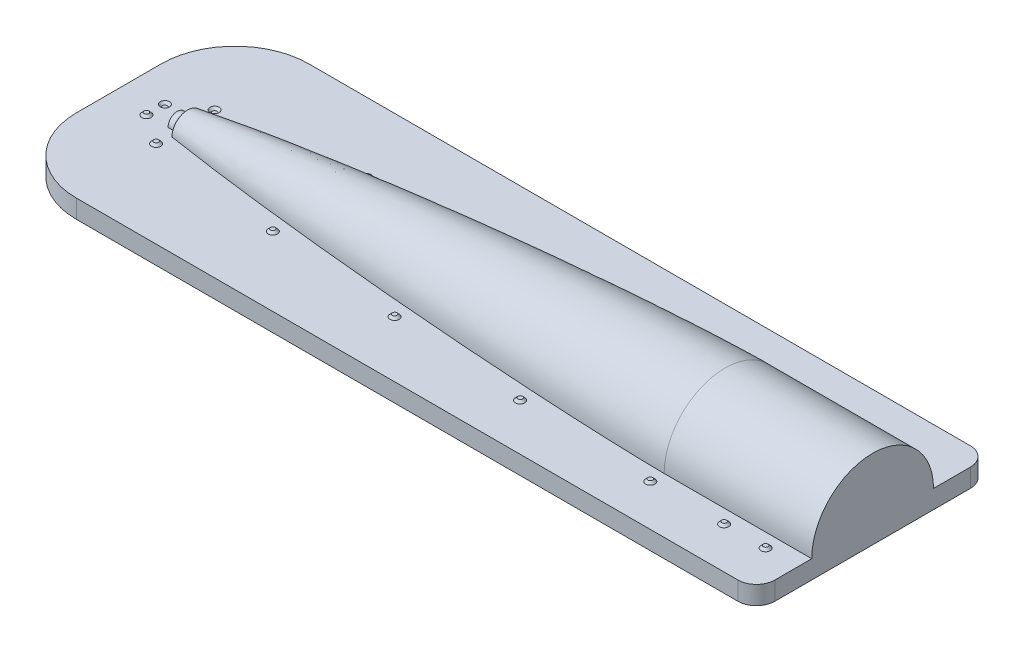
SolidWorks part; units mm, degrees
ref_plane "Front" through (0, 0, 0) normal (0, 0, 1) x (1, 0, 0)
ref_plane "Top" through (0, 0, 0) normal (0, 1, 0) x (1, 0, 0)
ref_plane "Right" through (0, 0, 0) normal (1, 0, 0) x (0, 0, -1)
other "von Karman body"
sketch "Sketch1" plane through (0, 0, 0) normal (0, 1, 0) x (1, 0, 0)
  line L0 (838.2, 83.82) -> (1041.4, 83.82)
  line L1 (1041.4, 83.82) -> (1055.402, 4.4107)
  line L2 (1055.7879, 0) -> (79.7661, 0)
  line L3 (96.6803, 12.7) -> (83.9803, 12.7)
  line L4 (96.6803, 12.7) -> (98.2259, 21.4654)
  line L5 (83.9803, 12.7) -> (80.7329, 4.8601)
  line L6 (0, 0) -> (1055.7879, 0) construction
  line L7 (83.9803, 12.7) -> (82.9291, 18.9624) construction
  line L8 (79.7661, 0) -> (79.7661, 6.839) construction
  circle A0 centre (3.2859, 0) radius 1.5875 construction
  arc A1 (80.7329, 4.8601) -> (79.7661, 0) centre (92.4661, 0) ccw
  arc A2 (1055.402, 4.4107) -> (1055.7879, 0) centre (1030.3879, 0) cw
  spline S0 degree 4 poles (0.0014, -0.0139) (0.0044, -0.0057) (0.0116, 0.0101) (0.0314, 0.0387) (0.0663, 0.0774) (0.1098, 0.1198) (0.1756, 0.1763) (0.2578, 0.2402) (0.43, 0.3617) (0.6491, 0.4956) (0.898, 0.6345) (1.1966, 0.7887) (1.4641, 0.9197) (1.9053, 1.1256) (2.6908, 1.4661) (4.1174, 2.0276) (6.8315, 2.9752) (11.8195, 4.4991) (21.1817, 6.9737) (37.5192, 10.6769) (65.2764, 16.0894) (103.3878, 22.4749) (149.5828, 29.2977) (200.9556, 36.0951) (252.4018, 42.3062) (303.9044, 48.03) (355.4522, 53.3298) (407.0382, 58.2429) (458.6575, 62.7928) (510.3066, 66.9901) (561.9831, 70.8361) (613.6852, 74.3214) (665.4118, 77.4242) (710.6933, 79.7692) (749.5207, 81.4699) (780.8317, 82.597) (801.9098, 83.2137) (819.2261, 83.6007) (830.0679, 83.7618) (835.4892, 83.8132) (838.2, 83.82) knots 0 0 0 0 0 0.000041 0.000082 0.000164 0.000247 0.000329 0.000493 0.000658 0.001245 0.001545 0.001844 0.002251 0.002657 0.003853 0.005902 0.009516 0.016281 0.028569 0.051794 0.088907 0.150314 0.211721 0.273128 0.334535 0.395942 0.457348 0.518755 0.580162 0.641569 0.702976 0.764383 0.825789 0.887196 0.9179 0.948603 0.974302 0.987151 1 1 1 1 1 construction
  spline S1 degree 4 poles (98.2259, 21.4654) (104.6543, 22.4927) (123.8878, 25.4864) (155.972, 30.1431) (200.9556, 36.0951) (252.4018, 42.3062) (303.9044, 48.03) (355.4522, 53.3298) (407.0382, 58.2429) (458.6575, 62.7928) (510.3066, 66.9901) (561.9831, 70.8361) (613.6852, 74.3214) (665.4118, 77.4242) (710.6933, 79.7692) (749.5207, 81.4699) (780.8317, 82.597) (801.9098, 83.2137) (819.2261, 83.6007) (830.0679, 83.7618) (835.4892, 83.8132) (838.2, 83.82) knots 0.119456 0.119456 0.119456 0.119456 0.119456 0.150314 0.211721 0.273128 0.334535 0.395942 0.457348 0.518755 0.580162 0.641569 0.702976 0.764383 0.825789 0.887196 0.9179 0.948603 0.974302 0.987151 1 1 1 1 1
  spline S2 degree 4 poles (0, 0) (0.003, 0.0082) (0.0102, 0.024) (0.03, 0.0526) (0.0649, 0.0913) (0.1084, 0.1337) (0.1742, 0.1902) (0.2565, 0.254) (0.4287, 0.3755) (0.6477, 0.5094) (0.8967, 0.6483) (1.1954, 0.8025) (1.4629, 0.9334) (1.9041, 1.1393) (2.6896, 1.4796) (4.1163, 2.0409) (6.8305, 2.9882) (11.8188, 4.5114) (21.1813, 6.9846) (37.5193, 10.6856) (65.2772, 16.0943) (103.3896, 22.4744) (149.5855, 29.2908) (200.9592, 36.0811) (252.4063, 42.285) (303.9097, 48.0016) (355.4582, 53.2943) (407.0449, 58.2003) (458.6648, 62.7429) (510.3146, 66.9331) (561.9916, 70.772) (613.6942, 74.2501) (665.4211, 77.3457) (710.703, 79.6843) (749.5307, 81.3797) (780.8418, 82.5024) (801.92, 83.1162) (819.2363, 83.5008) (830.0782, 83.6603) (835.4995, 83.711) (838.2103, 83.7174) knots 0 0 0 0 0 0.000041 0.000082 0.000164 0.000247 0.000329 0.000493 0.000658 0.001245 0.001545 0.001844 0.002251 0.002657 0.003853 0.005902 0.009516 0.016281 0.028569 0.051794 0.088907 0.150314 0.211721 0.273128 0.334535 0.395942 0.457348 0.518755 0.580162 0.641569 0.702976 0.764383 0.825789 0.887196 0.9179 0.948603 0.974302 0.987151 1 1 1 1 1 construction
  spline S3 degree 4 poles (0, 0) (0.003, 0.0082) (0.0102, 0.024) (0.03, 0.0526) (0.0649, 0.0913) (0.1084, 0.1337) (0.1742, 0.1902) (0.2565, 0.254) (0.4287, 0.3755) (0.6477, 0.5094) (0.8967, 0.6483) (1.1954, 0.8025) (1.4629, 0.9334) (1.9041, 1.1393) (2.6896, 1.4796) (4.1163, 2.0409) (6.8305, 2.9882) (11.8188, 4.5114) (21.1813, 6.9846) (37.5193, 10.6856) (58.8862, 14.849) (77.7757, 18.1421) (91.8621, 20.4493) (98.2259, 21.4654) knots 0 0 0 0 0 0.000041 0.000082 0.000164 0.000247 0.000329 0.000493 0.000658 0.001245 0.001545 0.001844 0.002251 0.002657 0.003853 0.005902 0.009516 0.016281 0.028569 0.051794 0.088907 0.119454 0.119454 0.119454 0.119454 0.119454 construction
  point P5 (0, 0)
  dimension "D6" = 3.175
  dimension "D9" = 25.4
  dimension "D10" = 12.7
  dimension "D1" = 12.7
  dimension "D2" = 100
  dimension "D3" = 203.2
  dimension "D4" = 6.35
  dimension "D5" = 838.2
  dimension "D7" = 67.5
  dimension "D8" = 80
  dimension "D11" = 83.82
  dimension "D12" = 12.7
revolve "main body" add sketch "Sketch1" angle 180 about L2 other way angle 180 reverse direction yes
scale "Scale1" [suppressed]
sketch "Sketch2" plane through (0, 0, 0) normal (0, -1, 0) x (1, 0, 0)
  line L0 (1055.7879, 0) -> (1131.9879, 0) construction
  line L1 (1131.9879, -160.02) -> (3.5661, -160.02)
  line L2 (1131.9879, -160.02) -> (1131.9879, 160.02)
  line L3 (1131.9879, 160.02) -> (3.5661, 160.02)
  line L4 (3.5661, -160.02) -> (3.5661, 160.02)
  line L5 (1041.4, -83.82) -> (838.2, -83.82) construction
  arc A0 (1055.402, -4.4107) -> (1055.402, 4.4107) centre (1030.3879, 0) ccw construction
  arc A1 (80.7329, 4.8601) -> (80.7329, -4.8601) centre (92.4661, 0) ccw construction
  point P17 (79.7661, 0)
  dimension "D2" = 76.2
  dimension "D1" = 76.2
  dimension "D3" = 76.2
extrude "Boss-Extrude1" add sketch "Sketch2" along normal blind 25.4
fillet "Fillet1" radius 6.35 1 edges at (96.6803, 12.7, 0)
sketch "Sketch3" plane through (0, 0, 0) normal (0, 1, 0) x (1, 0, 0)
  line L0 (79.7661, 0) -> (3.5661, 0) construction
  line L3 (3.5661, -160.02) -> (3.5661, 160.02) construction
  line L4 (95.2196, -40.2767) -> (98.2259, -21.4654) construction
  line L5 (282.229, -45.582) -> (280.1341, -64.5165) construction
  line L6 (465.7678, -82.4343) -> (467.3539, -63.4504) construction
  line L7 (651.796, -95.6427) -> (652.8954, -76.6245) construction
  line L8 (838.1523, -102.8699) -> (838.2, -83.82) construction
  line L9 (1041.4, -83.82) -> (838.2, -83.82) construction
  line L10 (996.95, -102.87) -> (996.95, -83.82) construction
  line L11 (1055.7879, 0) -> (1131.9879, 0) construction
  line L12 (1131.9879, 160.02) -> (1131.9879, -160.02) construction
  line L13 (1067.1616, -47.4233) -> (1048.401, -44.1153) construction
  line L14 (1055.402, -4.4107) -> (1041.4, -83.82) construction
  line L15 (95.2196, -40.2767) -> (280.1341, -64.5165) construction
  line L16 (280.1341, -64.5165) -> (465.7678, -82.4343) construction
  line L17 (465.7678, -82.4343) -> (651.796, -95.6427) construction
  line L18 (651.796, -95.6427) -> (838.1523, -102.8699) construction
  line L19 (939.8, -102.87) -> (939.8, -83.82) construction
  circle A0 centre (996.95, -102.87) radius 6.35
  circle A1 centre (838.1523, -102.8699) radius 6.35
  circle A2 centre (95.2196, -40.2767) radius 6.35
  circle A3 centre (465.7678, -82.4343) radius 6.35
  circle A4 centre (280.1341, -64.5165) radius 6.35
  circle A5 centre (651.796, -95.6427) radius 6.35
  circle A6 centre (54.3661, -12.7) radius 6.35
  circle A7 centre (1067.1616, -47.4233) radius 6.35
  arc A9 (80.7329, 4.8601) -> (80.7329, -4.8601) centre (92.4661, 0) ccw construction
  arc A10 (1055.402, -4.4107) -> (1055.402, 4.4107) centre (1030.3879, 0) ccw construction
  circle A11 centre (939.8, -102.87) radius 6.35
  spline S0 degree 4 poles (838.2, -83.82) (835.4892, -83.8132) (830.0679, -83.7618) (819.2261, -83.6007) (801.9098, -83.2137) (780.8317, -82.597) (749.5207, -81.4699) (710.6933, -79.7692) (665.4118, -77.4242) (613.6852, -74.3214) (561.9831, -70.8361) (510.3066, -66.9901) (458.6575, -62.7928) (407.0382, -58.2429) (355.4522, -53.3298) (303.9044, -48.03) (252.4018, -42.3062) (200.9556, -36.0951) (155.972, -30.1431) (123.8878, -25.4864) (104.6543, -22.4927) (98.2259, -21.4654) knots 0.119456 0.119456 0.119456 0.119456 0.119456 0.132305 0.145154 0.170853 0.201556 0.23226 0.293667 0.355073 0.41648 0.477887 0.539294 0.600701 0.662108 0.723514 0.784921 0.846328 0.907735 0.969142 1 1 1 1 1 construction
  point P34 (1006.8379, -102.1965)
  point P48 (939.8, -83.82)
  point P49 (1000.4634, -102.87)
  dimension "D1" = 12.7
  dimension "D2" = 12.7
  dimension "D3" = 25.4
  dimension "D4" = 19.05
  dimension "D5" = 57.15
extrude "Boss-Extrude2" add sketch "Sketch3" along normal blind 3.175 draft 45
sketch "Sketch4" plane through (0, 0, 0) normal (0, 1, 0) x (1, 0, 0)
  line L0 (3.5661, 0) -> (1131.9879, 0) construction
  line L1 (3.5661, -160.02) -> (3.5661, 160.02) construction
  line L2 (1131.9879, 160.02) -> (1131.9879, -160.02) construction
  circle A0 centre (996.95, 102.87) radius 6.35
  circle A1 centre (1067.1616, -47.4233) radius 6.35
  circle A2 centre (1067.1616, -47.4233) radius 6.35 construction
  circle A3 centre (54.3661, -12.7) radius 6.35
  circle A4 centre (54.3661, -12.7) radius 6.35 construction
  circle A5 centre (651.796, -95.6427) radius 6.35
  circle A6 centre (651.796, -95.6427) radius 6.35 construction
  circle A7 centre (280.1341, -64.5165) radius 6.35
  circle A8 centre (280.1341, -64.5165) radius 6.35 construction
  circle A9 centre (465.7678, -82.4343) radius 6.35
  circle A10 centre (465.7678, -82.4343) radius 6.35 construction
  circle A11 centre (95.2196, -40.2767) radius 6.35
  circle A12 centre (95.2196, -40.2767) radius 6.35 construction
  circle A13 centre (838.1523, -102.8699) radius 6.35
  circle A14 centre (838.1523, -102.8699) radius 6.35 construction
  circle A15 centre (996.95, -102.87) radius 6.35
  circle A16 centre (996.95, -102.87) radius 6.35 construction
  circle A17 centre (838.1523, 102.8699) radius 6.35
  circle A18 centre (95.2196, 40.2767) radius 6.35
  circle A19 centre (465.7678, 82.4343) radius 6.35
  circle A20 centre (280.1341, 64.5165) radius 6.35
  circle A21 centre (651.796, 95.6427) radius 6.35
  circle A22 centre (54.3661, 12.7) radius 6.35
  circle A23 centre (1067.1616, 47.4233) radius 6.35
  circle A24 centre (939.8, 102.87) radius 6.35
  circle A25 centre (939.8, -102.87) radius 6.35
  circle A26 centre (939.8, -102.87) radius 6.35 construction
  dimension "D1" = 0
  dimension "D2" = 0
  dimension "D3" = 0
  dimension "D4" = 0
  dimension "D5" = 0
  dimension "D6" = 0
  dimension "D7" = 0
  dimension "D8" = 0
  dimension "D9" = 0
extrude "Cut-Extrude1" cut sketch "Sketch4" against normal blind 3.175 draft 45
sketch "Sketch5" plane through (1131.9879, 0, 0) normal (1, 0, 0) x (0, 0, -1)
  line L1 (228.0392, 118.5985) -> (-235.7612, 118.5985)
  line L2 (228.0392, 118.5985) -> (228.0392, -74.0127)
  line L3 (228.0392, -74.0127) -> (-235.7612, -74.0127)
  line L4 (-235.7612, 118.5985) -> (-235.7612, -74.0127)
extrude "Cut-Extrude2" cut sketch "Sketch5" along direction (-1, 0, 0) on the side against the normal up to vertex (90.5879 mm away) up to point (1041.4, 0, 83.82)
fillet "Fillet2" radius 25.4 2 edges at (1041.4, -12.7, -160.02) (1041.4, -12.7, 160.02)
fillet "Fillet3" radius 101.6 2 edges at (3.5661, -12.7, 160.02) (3.5661, -12.7, -160.02)
